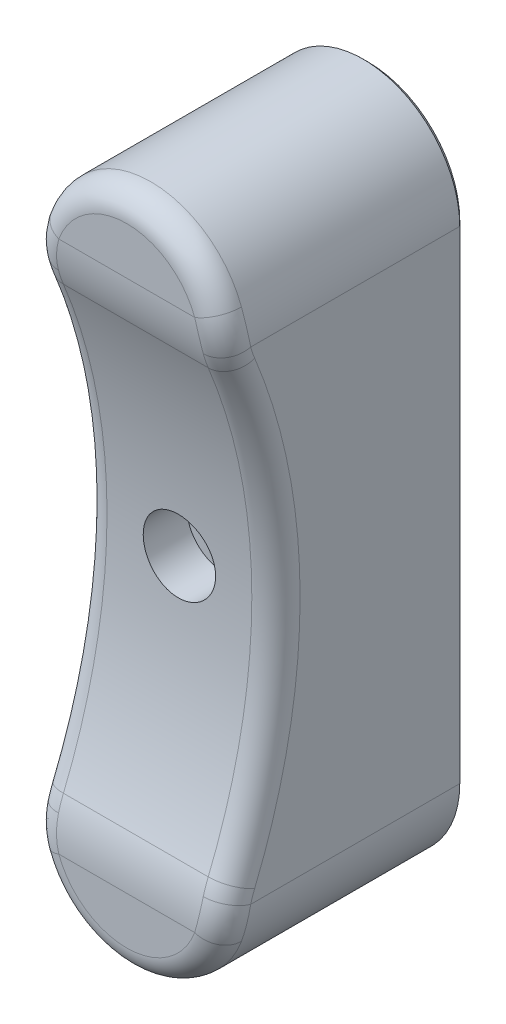
SolidWorks part; units mm, degrees
ref_plane "Front Plane" through (0, 0, 0) normal (0, 0, 1) x (1, 0, 0)
ref_plane "Top Plane" through (0, 0, 0) normal (0, 1, 0) x (1, 0, 0)
ref_plane "Right Plane" through (0, 0, 0) normal (1, 0, 0) x (0, 0, -1)
sketch "Sketch1" plane through (0, 0, 0) normal (0, 0, 1) x (1, 0, 0)
  line L0 (0, 50) -> (0, -50) construction
  line L1 (20, 50) -> (20, -50)
  line L2 (-20, 50) -> (-20, -50)
  arc A0 (20, 50) -> (-20, 50) centre (0, 50) ccw
  arc A1 (-20, -50) -> (20, -50) centre (0, -50) ccw
  point P3 (0, 0)
  dimension "D1" = 100
  dimension "D2" = 40
extrude "Boss-Extrude1" add sketch "Sketch1" along normal blind 50 from offset 1210
sketch "Sketch2" plane through (-20, 0, 0) normal (-1, 0, 0) x (0, 0, 1)
  line L0 (1260, 50) -> (1260, -50) construction
  line L1 (1260, 50) -> (1260, -50)
  arc A0 (1260, 50) -> (1260, -50) centre (1369.0871, 0) ccw
  dimension "D1" = 120
extrude "Cut-Extrude1" cut sketch "Sketch2" against normal blind 50
fillet "Fillet1" radius 25 2 edges at (0, -50, 1260) (0, 50, 1260)
fillet "Fillet2" radius 5 12 edges at (20, 47.8058, 1258.8854) (20, 0, 1249.0871) (20, -47.8058, 1258.8854) (0, -70, 1260) (-20, -47.8058, 1258.8854) (-20, 0, 1249.0871) (-20, 47.8058, 1258.8854) (0, 70, 1260)
chamfer "Chamfer1" distance 1 angle 45 4 edges at (20, 0, 1210) (0, 70, 1210) (0, -70, 1210) (-20, 0, 1210)
sketch "Sketch3" plane through (0, 0, 1210) normal (0, 0, -1) x (-1, 0, 0)
  circle A0 centre (0, 0) radius 4.25
  dimension "D1" = 8.5
extrude "Cut-Extrude2" cut sketch "Sketch3" against normal blind 50
sketch "Sketch4" plane through (0, 0, 1210) normal (0, 0, -1) x (-1, 0, 0)
  circle A0 centre (0, 0) radius 7.5
  dimension "D1" = 15
extrude "Cut-Extrude3" cut sketch "Sketch4" against normal blind 50 from offset 30 offset against normal yes
